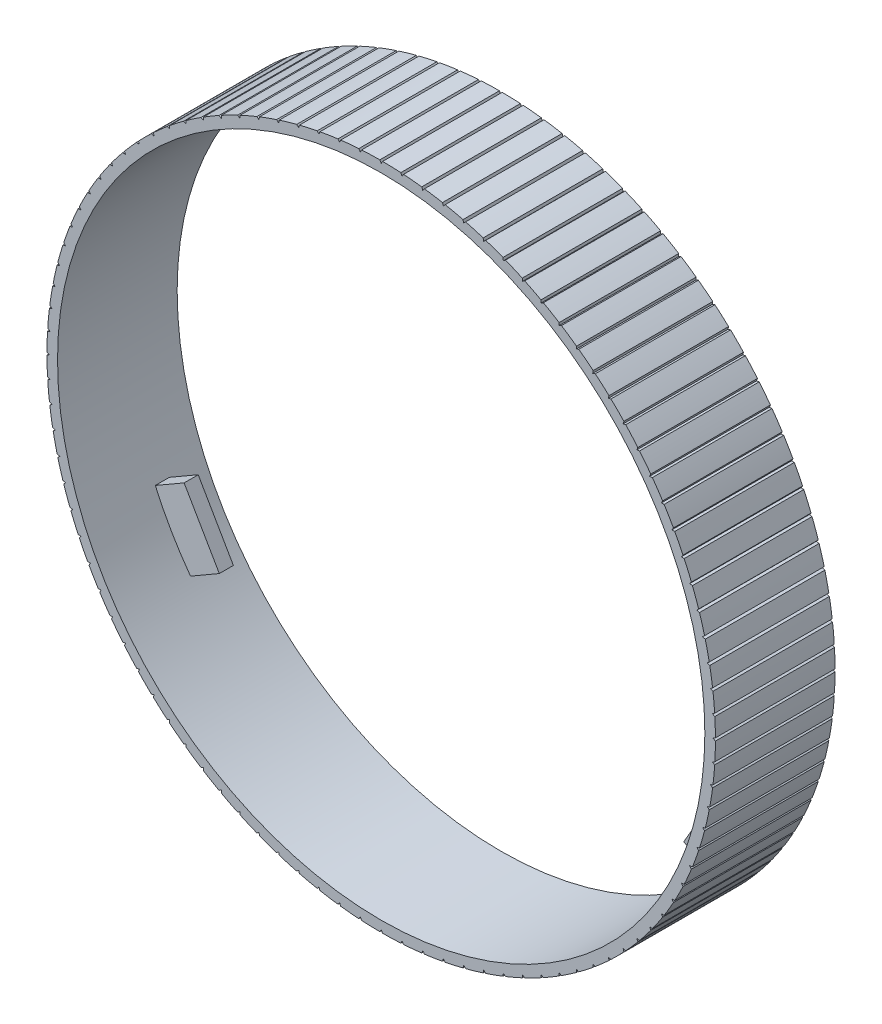
SolidWorks part; units mm, degrees
material "ABS"
ref_plane "Front Plane" through (0, 0, 0) normal (0, 0, 1) x (1, 0, 0)
ref_plane "Top Plane" through (0, 0, 0) normal (0, 1, 0) x (1, 0, 0)
ref_plane "Right Plane" through (0, 0, 0) normal (1, 0, 0) x (0, 0, -1)
sketch "Sketch2" plane through (0, 0, 0) normal (0, 0, 1) x (1, 0, 0)
  line L0 (0, 0) -> (0, 46) construction
  line L2 (5, 41) -> (-5, 41)
  line L3 (5, 41) -> (5, 46)
  line L4 (5, 46) -> (-5, 46)
  line L5 (-5, 41) -> (-5, 46)
  line L6 (5, 41) -> (-5, 46) construction
  line L7 (5, 46) -> (-5, 41) construction
  circle A0 centre (0, 0) radius 46
  circle A1 centre (0, 0) radius 47.5
  point P4 (0, 43.5)
  dimension "D1" = 92
  dimension "D2" = 95
  dimension "D3" = 10
  dimension "D4" = 5
extrude "Boss-Extrude1" add sketch "Sketch2" along normal blind 11 and the other way blind 6 contours A1 A0 L5 L4 L3 | A0 L3 L4 | A0 L4 L5 region at (3.7507, 45.9183, 0) region at (-3.7507, 45.9183, 0) region at (-46.1565, 0, 0)
extrude "Boss-Extrude2" add sketch "Sketch2<4>" along normal mid plane 2 contours L3 A0 L5 L2 | A0 L4 L5 | A0 L3 L4 region at (0, 43.4553, 0) region at (3.7507, 45.9183, 0) region at (-3.7507, 45.9183, 0)
sketch "Sketch2<4>" plane through (0, 0, 0) normal (0, 0, 1) x (1, 0, 0) same geometry as "Sketch2"
pattern_circular "CirPattern1" count 3 over 360 about axis through (0, 0, -6) along (0, 0, 1) of "Boss-Extrude2"
sketch "Sketch3" plane through (0, 0, -6) normal (0, 0, -1) x (-1, 0, 0)
  line L0 (0, 0) -> (54.1037, 0) construction
  line L2 (47.6686, -0.292) -> (47.6686, 0.292)
  line L3 (47.6686, 0.292) -> (47.1628, 0)
  line L4 (47.1628, 0) -> (47.6686, -0.292)
  circle A0 centre (47.5, 0) radius 0.1686 construction
  circle A1 centre (0, 0) radius 47.5 construction
  dimension "D1" = 0.3372
extrude "Cut-Extrude1" cut sketch "Sketch3" against normal through all
pattern_circular "CirPattern2" count 100 over 360 about axis through (0, 0, -6) along (0, 0, 1) of "Cut-Extrude1"
